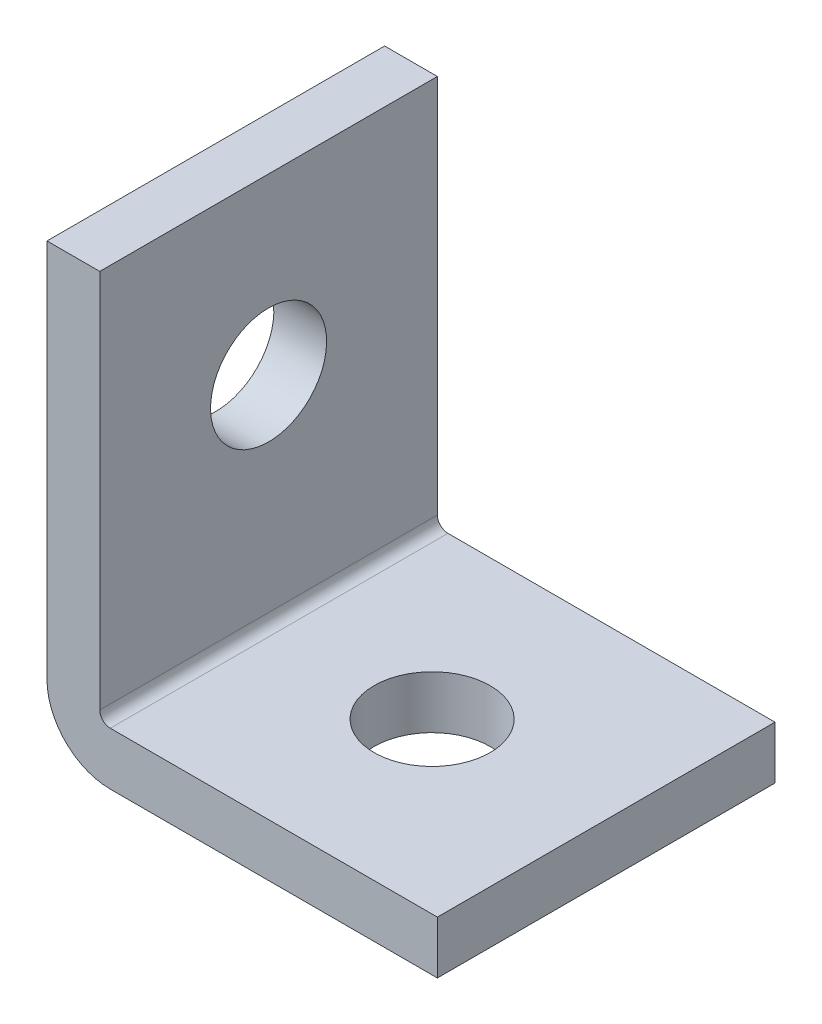
SolidWorks part; units mm, degrees
ref_plane "Front Plane" through (0, 0, 0) normal (0, 0, 1) x (1, 0, 0)
ref_plane "Top Plane" through (0, 0, 0) normal (0, 1, 0) x (1, 0, 0)
ref_plane "Right Plane" through (0, 0, 0) normal (1, 0, 0) x (0, 0, -1)
sketch "Sketch1" plane through (0, 0, 0) normal (0, 0, 1) x (1, 0, 0)
  line L0 (0, 1.27) -> (0, 46.99)
  line L1 (0, 46.99) -> (-6.35, 46.99)
  line L2 (-6.35, 46.99) -> (-6.35, 1.27)
  line L3 (1.27, -6.35) -> (40.64, -6.35)
  line L4 (40.64, -6.35) -> (40.64, 0)
  line L5 (40.64, 0) -> (1.27, 0)
  arc A0 (-6.35, 1.27) -> (1.27, -6.35) centre (1.27, 1.27) ccw
  arc A1 (0, 1.27) -> (1.27, 0) centre (1.27, 1.27) ccw
  point P12 (0, 0)
  dimension "D4" = 7.62
  dimension "D5" = 1.27
  dimension "D1" = 6.35
  dimension "D2" = 53.34
  dimension "D3" = 46.99
extrude "Boss-Extrude1" add sketch "Sketch1" along normal mid plane 40.64
sketch "Sketch2" plane through (0, 0, 0) normal (1, 0, 0) x (0, 0, -1)
  line L0 (-20.32, 46.99) -> (20.32, 46.99) construction
  circle A0 centre (0, 26.035) radius 6.985
  point P0 (0, 0)
  dimension "D1" = 13.97
  dimension "D2" = 13.97
extrude "Cut-Extrude1" cut sketch "Sketch2" against normal up to next
sketch "Sketch3" plane through (0, 0, 0) normal (0, 1, 0) x (1, 0, 0)
  line L0 (40.64, -20.32) -> (40.64, 20.32) construction
  circle A0 centre (19.685, 0) radius 6.985
  point P2 (0, 0)
  dimension "D1" = 13.97
  dimension "D2" = 13.97
extrude "Cut-Extrude2" cut sketch "Sketch3" against normal up to next
